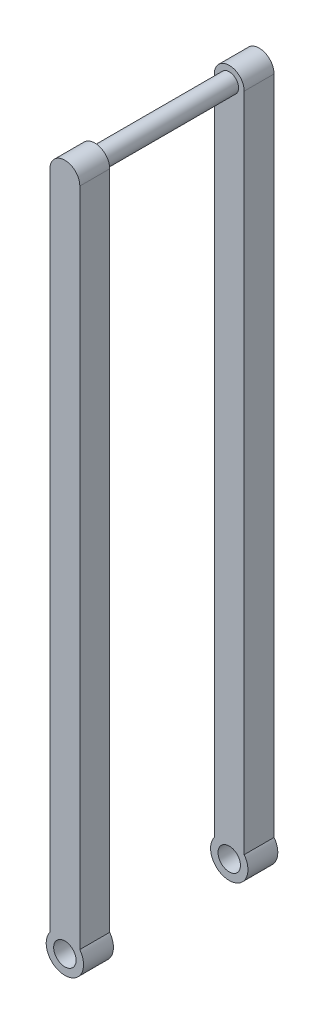
SolidWorks part; units mm, degrees
ref_plane "Front Plane" through (0, 0, 0) normal (0, 0, 1) x (1, 0, 0)
ref_plane "Top Plane" through (0, 0, 0) normal (0, 1, 0) x (1, 0, 0)
ref_plane "Right Plane" through (0, 0, 0) normal (1, 0, 0) x (0, 0, -1)
sketch "Sketch1" plane through (0, 0, 0) normal (0, 0, 1) x (1, 0, 0)
  line L0 (2, 0) -> (2, 90) construction
  line L1 (-2, 0) -> (-2, 90) construction
  line L2 (-2, 90) -> (-2, 1.5)
  line L3 (2, 90) -> (2, 1.5)
  circle A0 centre (0, 0) radius 1.5
  circle A1 centre (0, 0) radius 2.5 construction
  circle A2 centre (0, 0) radius 2 construction
  arc A4 (-2, 90) -> (2, 90) centre (0, 90) cw
  arc A5 (2, 1.5) -> (-2, 1.5) centre (0, 0) cw
  circle A7 centre (0, 90) radius 1.25
  dimension "D1" = 3
  dimension "D2" = 1
  dimension "D3" = 4
  dimension "D6" = 2.5
  dimension "D4" = 90
  dimension "D5" = 90
extrude "Boss-Extrude1" add sketch "Sketch1" along normal blind 2 and the other way blind 2 contours A7 | A5 L3 A4 L2 A7 A0 region at (0, 44.6924, 0) region at (0, 90, 0)
ref_plane "Plane1" through (0, 0, 11) normal (0, 0, 1) x (1, 0, 0)
mirror "Mirror2" about plane through (0, 0, 11) normal (0, 0, 1) of bodies 101
extrude "Boss-Extrude2" add sketch "Sketch1<4>" along normal up to surface (20 mm away) contours A7 up to face at (0, 45.25, 20)
sketch "Sketch1<4>" plane through (0, 0, 0) normal (0, 0, 1) x (1, 0, 0) same geometry as "Sketch1"
